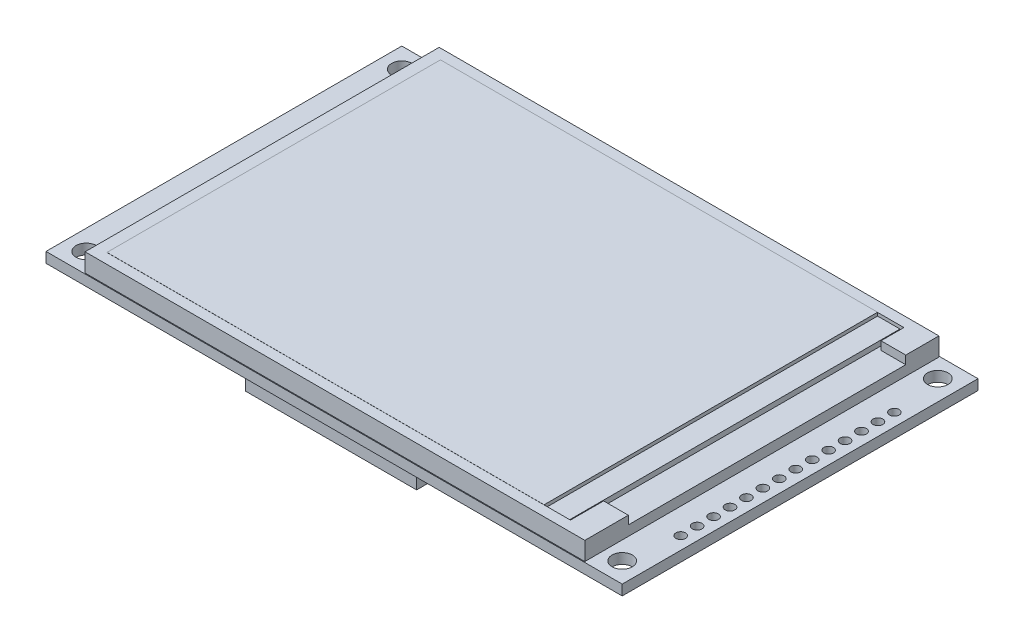
SolidWorks part; units mm, degrees
ref_plane "Plan de face" through (0, 0, 0) normal (0, 0, 1) x (1, 0, 0)
ref_plane "Plan de dessus" through (0, 0, 0) normal (0, 1, 0) x (1, 0, 0)
ref_plane "Plan de droite" through (0, 0, 0) normal (1, 0, 0) x (0, 0, -1)
sketch "Esquisse1" plane through (0, 0, 0) normal (0, 1, 0) x (1, 0, 0)
  line L1 (-44.7, -27.6) -> (44.7, -27.6)
  line L2 (-44.7, -27.6) -> (-44.7, 27.6)
  line L3 (-44.7, 27.6) -> (44.7, 27.6)
  line L4 (44.7, -27.6) -> (44.7, 27.6)
  line L5 (-44.7, -27.6) -> (44.7, 27.6) construction
  line L6 (-44.7, 27.6) -> (44.7, -27.6) construction
  circle A0 centre (-41.58, 24.48) radius 1.58
  circle A1 centre (41.58, 24.48) radius 1.58
  circle A2 centre (-41.58, -24.48) radius 1.58
  circle A3 centre (41.58, -24.48) radius 1.58
  point P0 (0, 0)
  point P8 (-41.58, 26.06)
  point P9 (-43.16, 24.48)
  point P12 (41.58, 26.06)
  point P13 (43.16, 24.48)
  point P16 (-43.16, -24.48)
  point P17 (-41.58, -26.06)
  point P20 (43.16, -24.48)
  point P21 (41.58, -26.06)
  dimension "D3" = 3.16
  dimension "D6" = 3.16
  dimension "D9" = 3.16
  dimension "D12" = 3.16
  dimension "D1" = 89.4
  dimension "D2" = 55.2
  dimension "D4" = 1.54
  dimension "D5" = 1.54
  dimension "D7" = 1.54
  dimension "D8" = 1.54
  dimension "D10" = 1.54
  dimension "D11" = 1.54
  dimension "D13" = 1.54
  dimension "D14" = 1.54
extrude "Plaque" add sketch "Esquisse1" along normal blind 1.6
sketch "Esquisse2" plane through (0, 1.6, 0) normal (0, 1, 0) x (1, 0, 0)
  line L0 (34.9348, -25.87) -> (34.9348, -20.72)
  line L1 (-38.77, -27.47) -> (38.77, -27.47)
  line L2 (-38.77, -27.47) -> (-38.77, 27.47)
  line L3 (-38.77, 27.47) -> (38.77, 27.47)
  line L4 (38.77, -27.47) -> (38.77, 27.47)
  line L5 (-38.77, -27.47) -> (38.77, 27.47) construction
  line L6 (-38.77, 27.47) -> (38.77, -27.47) construction
  line L7 (-36.97, 25.87) -> (-36.97, -25.87)
  line L8 (-36.97, -25.87) -> (34.9348, -25.87)
  line L9 (-36.97, 25.87) -> (34.9348, 25.87)
  line L10 (34.9348, 25.87) -> (34.9348, 22.32)
  line L11 (34.9348, 22.32) -> (38.77, 22.32)
  line L12 (34.9348, -20.72) -> (38.77, -20.72)
  line L13 (34.32, 25.87) -> (34.32, -25.87)
  line L14 (-36.97, 25.87) -> (30.85, 25.87)
  line L15 (-36.97, 25.87) -> (-36.97, -25.87)
  line L16 (-36.97, -25.87) -> (30.85, -25.87)
  line L17 (30.85, 25.87) -> (30.85, -25.87)
  point P0 (0, 0)
  dimension "D1" = 54.94
  dimension "D2" = 77.54
  dimension "D3" = 1.6
  dimension "D4" = 1.8
  dimension "D5" = 1.6
  dimension "D6" = 3.8352
  dimension "D7" = 5.15
  dimension "D8" = 5.15
  dimension "D9" = 67.82
  dimension "D10" = 4.45
extrude "Nappe" add sketch "Esquisse2<3>" along normal blind 2.35 contours L9 L17 L8 L13 region at (32.585, 1.6, 0)
sketch "Esquisse2<3>" plane through (0, 1.6, 0) normal (0, 1, 0) x (1, 0, 0) same geometry as "Esquisse2"
extrude "Bordure" add sketch "Esquisse2<5>" along normal blind 2.85 contours L12 L0 L8 L7 L9 L10 L11 L4 L3 L2 L1 region at (35.8851, 1.6, 23.295)
sketch "Esquisse2<5>" plane through (0, 1.6, 0) normal (0, 1, 0) x (1, 0, 0) same geometry as "Esquisse2"
extrude "LCD" add sketch "Esquisse2" along normal blind 2.87 contours L17 L9 L7 L8 region at (-3.06, 1.6, 0)
extrude "Support" add sketch "Esquisse2<8>" along normal blind 1.55 contours L9 L13 L8 L0 L12 L4 L11 L10 region at (36.4929, 1.6, -0.6707)
sketch "Esquisse2<8>" plane through (0, 1.6, 0) normal (0, 1, 0) x (1, 0, 0) same geometry as "Esquisse2"
sketch "Esquisse4" plane through (0, 0, 0) normal (0, -1, 0) x (1, 0, 0)
  line L0 (-15.04, 26.3) -> (11.5, 26.3)
  line L1 (11.5, 26.3) -> (11.5, 9.7)
  line L2 (11.5, 9.7) -> (-12.95, 9.7)
  line L3 (-12.95, 9.7) -> (-12.95, 15.2829)
  line L4 (-12.95, 15.2829) -> (-15.04, 17.5581)
  line L5 (-15.04, 17.5581) -> (-15.04, 26.3)
  line L6 (44.7, 27.6) -> (44.7, -27.6) construction
  line L7 (-44.7, 27.6) -> (44.7, 27.6) construction
  dimension "D1" = 26.54
  dimension "D2" = 16.6
  dimension "D3" = 24.45
  dimension "D4" = 33.2
  dimension "D5" = 1.3
extrude "Carte SD" add sketch "Esquisse4" along normal blind 3
sketch "Esquisse5" plane through (0, 1.6, 0) normal (0, 1, 0) x (1, 0, 0)
  line L0 (44.7, 27.6) -> (-44.7, 27.6) construction
  circle A0 centre (42.7247, 16.6) radius 0.75
  circle A1 centre (42.7247, 14.05) radius 0.75
  circle A2 centre (42.7247, 11.5) radius 0.75
  circle A3 centre (42.7247, 8.95) radius 0.75
  circle A4 centre (42.7247, 6.4) radius 0.75
  circle A5 centre (42.7247, 3.85) radius 0.75
  circle A6 centre (42.7247, 1.3) radius 0.75
  circle A7 centre (42.7247, -1.25) radius 0.75
  circle A8 centre (42.7247, -3.8) radius 0.75
  circle A9 centre (42.7247, -6.35) radius 0.75
  circle A10 centre (42.7247, -8.9) radius 0.75
  circle A11 centre (42.7247, -11.45) radius 0.75
  circle A12 centre (42.7247, -14) radius 0.75
  circle A13 centre (42.7247, -16.55) radius 0.75
  point P2 (43.4747, 16.6)
  point P3 (42.7247, 17.35)
  point P34 (42.7247, -17.3)
  dimension "D1" = 1.5
  dimension "D2" = 10.25
  dimension "D3" = 14
extrude "Enlèv. mat.-Extru.1" cut sketch "Esquisse5" against normal through all
